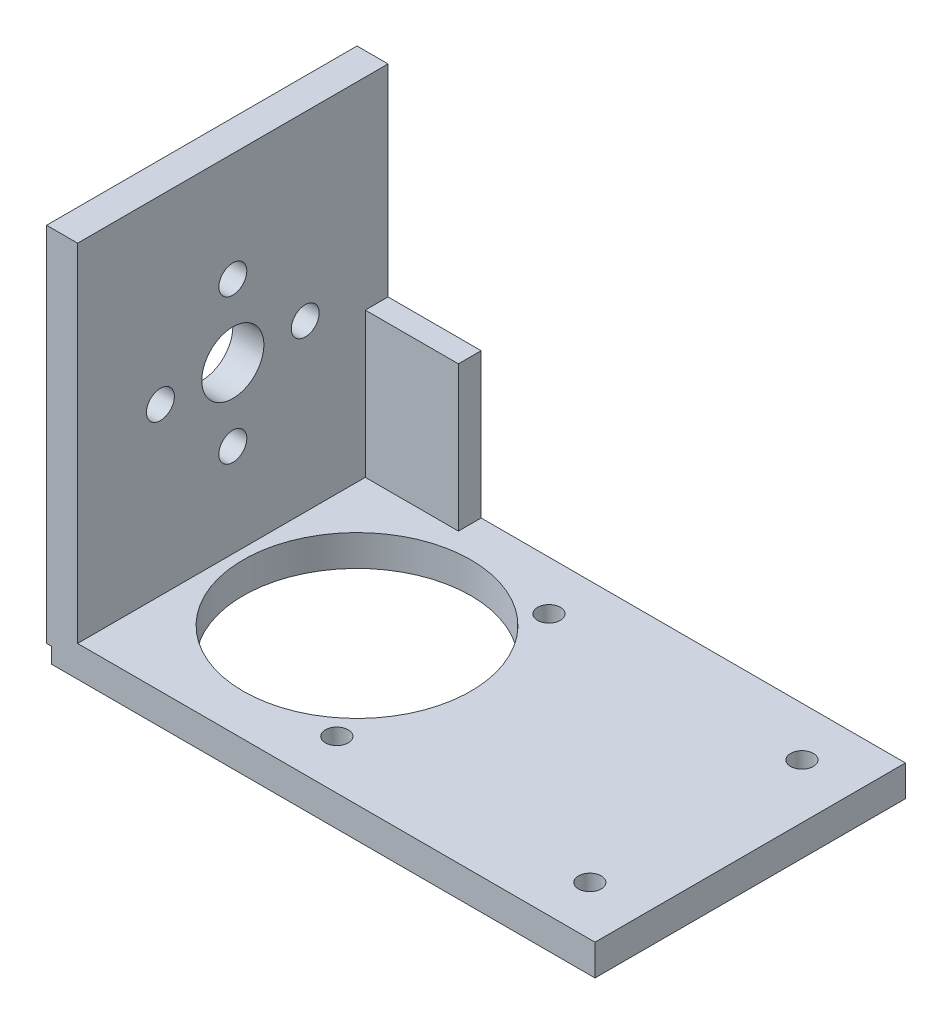
SolidWorks part; units mm, degrees
ref_plane "Front Plane" through (0, 0, 0) normal (0, 0, 1) x (1, 0, 0)
ref_plane "Top Plane" through (0, 0, 0) normal (0, 1, 0) x (1, 0, 0)
ref_plane "Right Plane" through (0, 0, 0) normal (1, 0, 0) x (0, 0, -1)
ref_plane "PZ_m15_000" through (0, 0, -15) normal (0, 0, 1) x (1, 0, 0)
sketch "S_box1" plane through (0, 0, -15) normal (0, 0, 1) x (1, 0, 0)
  line L0 (-15, -17.5) -> (-12, -17.5)
  line L1 (-12, -17.5) -> (-12, 17.5)
  line L2 (-12, 17.5) -> (-15, 17.5)
  line L3 (-15, 17.5) -> (-15, -17.5)
  dimension "P1" = 15
  dimension "P2" = 17.5
  dimension "P3" = 12
  dimension "P4" = 17.5
  dimension "P5" = 12
  dimension "P6" = 17.5
  dimension "P7" = 15
  dimension "P8" = 17.5
extrude "Boss_1" add sketch "S_box1" along normal blind 30
sketch "S_box2" plane through (0, 0, -15) normal (0, 0, 1) x (1, 0, 0)
  line L0 (-14.5, -19) -> (38, -19)
  line L1 (38, -19) -> (38, -16)
  line L2 (38, -16) -> (-14.5, -16)
  line L3 (-14.5, -16) -> (-14.5, -19)
  dimension "P1" = 14.5
  dimension "P2" = 19
  dimension "P3" = 38
  dimension "P4" = 19
  dimension "P5" = 38
  dimension "P6" = 16
  dimension "P7" = 14.5
  dimension "P8" = 16
extrude "Boss_2" add sketch "S_box2" along normal blind 30
sketch "S_box3" plane through (0, 0, -15) normal (0, 0, 1) x (1, 0, 0)
  line L0 (-14.5, -18.5) -> (-3, -18.5)
  line L1 (-3, -18.5) -> (-3, -2)
  line L2 (-3, -2) -> (-14.5, -2)
  line L3 (-14.5, -2) -> (-14.5, -18.5)
  dimension "P1" = 14.5
  dimension "P2" = 18.5
  dimension "P3" = 3
  dimension "P4" = 18.5
  dimension "P5" = 3
  dimension "P6" = 2
  dimension "P7" = 14.5
  dimension "P8" = 2
extrude "Boss_3" add sketch "S_box3" along normal blind 2.2
ref_plane "PX_m15_100" through (-15.1, 0, 0) normal (1, 0, 0) x (0, 0, -1)
sketch "S_hole4" plane through (-15.1, 0, 0) normal (1, 0, 0) x (0, 0, -1)
  circle A0 centre (0, 0) radius 3
  dimension "D1_S_hole4" = 6
extrude "Hole_4" cut sketch "S_hole4" along normal blind 3.2
sketch "S_hole5" plane through (-15.1, 0, 0) normal (1, 0, 0) x (0, 0, -1)
  circle A0 centre (0, 7) radius 1.35
  dimension "D1_S_hole5" = 2.7
  dimension "P2" = 7
extrude "Hole_5" cut sketch "S_hole5" along normal blind 3.2
sketch "S_hole6" plane through (-15.1, 0, 0) normal (1, 0, 0) x (0, 0, -1)
  circle A0 centre (-7, 0) radius 1.35
  dimension "D1_S_hole6" = 2.7
  dimension "P2" = 7
extrude "Hole_6" cut sketch "S_hole6" along normal blind 3.2
sketch "S_hole7" plane through (-15.1, 0, 0) normal (1, 0, 0) x (0, 0, -1)
  circle A0 centre (0, -7) radius 1.35
  dimension "D1_S_hole7" = 2.7
  dimension "P2" = 7
extrude "Hole_7" cut sketch "S_hole7" along normal blind 3.2
sketch "S_hole8" plane through (-15.1, 0, 0) normal (1, 0, 0) x (0, 0, -1)
  circle A0 centre (7, 0) radius 1.35
  dimension "D1_S_hole8" = 2.7
  dimension "P2" = 7
extrude "Hole_8" cut sketch "S_hole8" along normal blind 3.2
ref_plane "PY_m19_100" through (0, -19.1, 0) normal (0, 1, 0) x (1, 0, 0)
sketch "S_hole9" plane through (0, -19.1, 0) normal (0, 1, 0) x (1, 0, 0)
  circle A0 centre (0, 0) radius 11
  dimension "D1_S_hole9" = 22
extrude "Hole_9" cut sketch "S_hole9" along normal blind 3.2
sketch "S_hole10" plane through (0, -19.1, 0) normal (0, 1, 0) x (1, 0, 0)
  circle A0 centre (8.3, 10.25) radius 1.1
  dimension "D1_S_hole10" = 2.2
  dimension "P2" = 8.3
  dimension "P3" = 10.25
extrude "Hole_10" cut sketch "S_hole10" along normal blind 3.2
sketch "S_hole11" plane through (0, -19.1, 0) normal (0, 1, 0) x (1, 0, 0)
  circle A0 centre (8.3, -10.25) radius 1.1
  dimension "D1_S_hole11" = 2.2
  dimension "P2" = 8.3
  dimension "P3" = 10.25
extrude "Hole_11" cut sketch "S_hole11" along normal blind 3.2
sketch "S_hole12" plane through (0, -19.1, 0) normal (0, 1, 0) x (1, 0, 0)
  circle A0 centre (32.75, 10.25) radius 1.1
  dimension "D1_S_hole12" = 2.2
  dimension "P2" = 32.75
  dimension "P3" = 10.25
extrude "Hole_12" cut sketch "S_hole12" along normal blind 3.2
sketch "S_hole13" plane through (0, -19.1, 0) normal (0, 1, 0) x (1, 0, 0)
  circle A0 centre (32.75, -10.25) radius 1.1
  dimension "D1_S_hole13" = 2.2
  dimension "P2" = 32.75
  dimension "P3" = 10.25
extrude "Hole_13" cut sketch "S_hole13" along normal blind 3.2
equation "\"plate_t\" = 3"
equation "\"clearance\" = 0.4"
